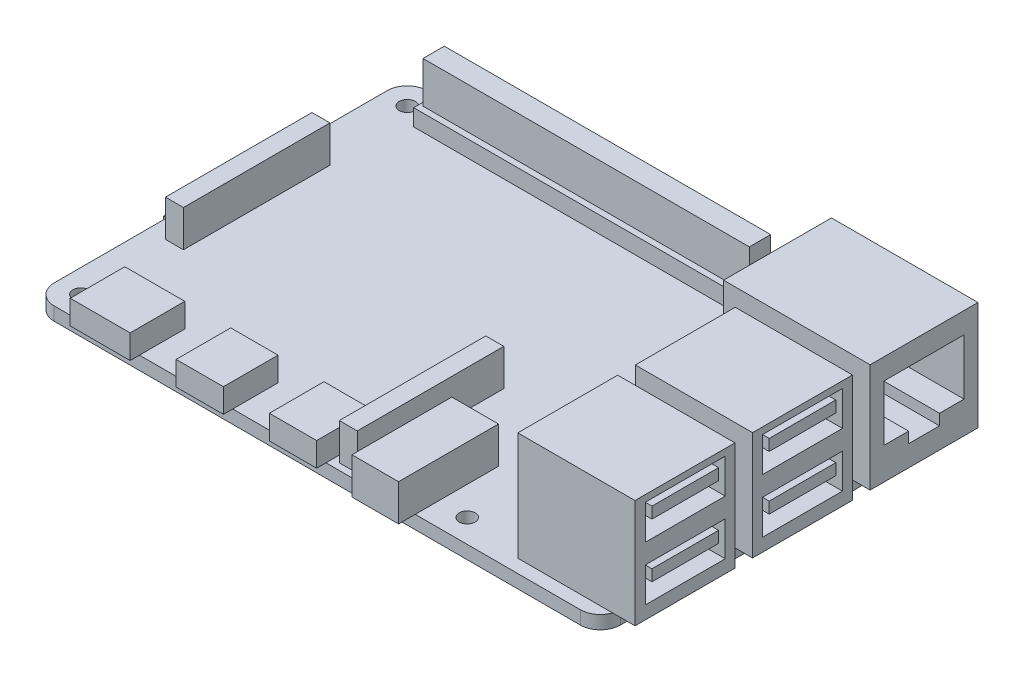
SolidWorks part; units mm, degrees
ref_plane "Plan de face" through (0, 0, 0) normal (0, 0, 1) x (1, 0, 0)
ref_plane "Plan de dessus" through (0, 0, 0) normal (0, 1, 0) x (1, 0, 0)
ref_plane "Plan de droite" through (0, 0, 0) normal (1, 0, 0) x (0, 0, -1)
sketch "Esquisse1" plane through (0, 0, 0) normal (0, 1, 0) x (1, 0, 0)
  line L1 (-42.5, 28) -> (42.5, 28)
  line L2 (-42.5, 28) -> (-42.5, -28)
  line L3 (-42.5, -28) -> (42.5, -28)
  line L4 (42.5, 28) -> (42.5, -28)
  line L5 (-42.5, 28) -> (42.5, -28) construction
  line L6 (-42.5, -28) -> (42.5, 28) construction
  point P0 (0, 0)
  dimension "D1" = 85
  dimension "D2" = 56
extrude "Boss.-Extru.1" add sketch "Esquisse1" along normal blind 2
hole_wizard "Dégagement M21" positions "Esquisse3D1" profile "Esquisse2" hole size "M2" standard "ISO" end condition up to next
sketch3d "Esquisse3D1"
  line L1 (-39, 2, -24.5) -> (-39, 2, 24.5)
  line L2 (-39, 2, -24.5) -> (19, 2, -24.5)
  line L3 (19, 2, -24.5) -> (19, 2, 24.5)
  line L4 (-39, 2, 24.5) -> (19, 2, 24.5)
  line L5 (-42.5, 2, -28) -> (-42.5, 2, 28) construction
  line L6 (42.5, 2, -28) -> (-42.5, 2, -28) construction
  point P0 (-39, 2, -24.5)
  point P2 (-39, 2, 24.5)
  point P4 (19, 2, -24.5)
  point P6 (19, 2, 24.5)
  dimension "D1" = 49
  dimension "D2" = 58
  dimension "D3" = 3.5
  dimension "D4" = 3.5
sketch "Esquisse2" plane through (-39, 2, -24.5) normal (1, 0, 0) x (0, 0, 1)
  line L0 (0, 0) -> (0, 2)
  line L1 (0, 2) -> (1.2, 2)
  line L2 (1.2, 2) -> (1.2, 0)
  line L5 (1.2, 0) -> (0, 0)
  line L11 (0, -6.35) -> (0, 107.95) construction
  dimension "Diamètre du perçage jusqu'au prochain" = 2.4
  dimension "Profondeur du perçage jusqu'au prochain" = 2
sketch "Esquisse4" plane through (0, 2, 0) normal (0, 1, 0) x (1, 0, 0)
  line L1 (-35.7959, 27.2655) -> (14.2041, 27.2655)
  line L2 (-35.7959, 27.2655) -> (-35.7959, 22.2655)
  line L3 (-35.7959, 22.2655) -> (14.2041, 22.2655)
  line L4 (14.2041, 27.2655) -> (14.2041, 22.2655)
  dimension "D1" = 5
  dimension "D2" = 50
extrude "Boss.-Extru.3" add sketch "Esquisse4" along normal blind 2.5
sketch "Esquisse6" plane through (0, 4.5, 0) normal (0, 1, 0) x (1, 0, 0)
  line L0 (-35.7959, 22.2655) -> (14.2041, 22.2655) construction
  line L1 (-35.2959, 26.3655) -> (13.7041, 26.3655)
  line L2 (-35.2959, 26.3655) -> (-35.2959, 23.1655)
  line L3 (-35.2959, 23.1655) -> (13.7041, 23.1655)
  line L4 (13.7041, 26.3655) -> (13.7041, 23.1655)
  line L5 (-35.7959, 27.2655) -> (-35.7959, 22.2655) construction
  point P4 (-10.7959, 23.1655)
  point P7 (-10.7959, 22.2655)
  point P8 (-35.2959, 24.7655)
  point P11 (-35.7959, 24.7655)
  dimension "D1" = 49
  dimension "D2" = 3.2
extrude "Boss.-Extru.5" add sketch "Esquisse6" along normal blind 6.2
sketch "Esquisse3" plane through (0, 2, 0) normal (0, 1, 0) x (1, 0, 0)
  line L0 (42.5, 28) -> (-42.5, 28) construction
  line L1 (23.7, 25.5) -> (45.7, 25.5)
  line L2 (23.7, 25.5) -> (23.7, 9.3)
  line L3 (28.1, -26) -> (45.7, -26)
  line L4 (45.7, 25.5) -> (45.7, 9.3)
  line L5 (-42.5, -28) -> (42.5, -28) construction
  line L6 (42.5, -28) -> (42.5, 28) construction
  line L7 (28.1, -11) -> (45.7, -11)
  line L8 (28.1, -8.35) -> (45.7, -8.35)
  line L9 (28.1, -11) -> (28.1, -26)
  line L10 (45.7, -11) -> (45.7, -26)
  line L11 (28.1, 6.65) -> (45.7, 6.65)
  line L12 (23.7, 9.3) -> (45.7, 9.3)
  line L13 (28.1, 6.65) -> (28.1, -8.35)
  line L14 (45.7, 6.65) -> (45.7, -8.35)
  line L15 (45.7, -11) -> (45.7, -8.35) construction
  line L16 (45.7, 6.65) -> (45.7, 9.3) construction
  dimension "D1" = 2.5
  dimension "D2" = 2
  dimension "D3" = 3.2
  dimension "D4" = 22
  dimension "D5" = 15
  dimension "D6" = 16.2
  dimension "D7" = 17.6
extrude "Boss.-Extru.2" add sketch "Esquisse3" along normal blind 16.3
sketch "Esquisse7" plane through (45.7, 0, 0) normal (1, 0, 0) x (0, 0, -1)
  line L6 (17.4, 5.15) -> (17.4, 15.15) construction
  line L7 (23.4, 15.15) -> (11.4, 15.15)
  line L8 (11.4, 15.15) -> (11.4, 6.7853)
  line L9 (11.4, 6.7853) -> (15.0804, 6.7853)
  line L10 (15.0804, 6.7853) -> (15.0804, 5.15)
  line L11 (15.0804, 5.15) -> (19.7196, 5.15)
  line L12 (19.7196, 6.7853) -> (19.7196, 5.15)
  line L13 (23.4, 6.7853) -> (19.7196, 6.7853)
  line L14 (23.4, 15.15) -> (23.4, 6.7853)
  line L15 (9.3, 18.3) -> (25.5, 18.3) construction
  line L16 (9.3, 18.3) -> (9.3, 2) construction
  line L17 (-8.35, 10.15) -> (-3.4275, 10.15) construction
  line L22 (-8.35, 18.3) -> (-8.35, 2) construction
  line L23 (-24.45, 17.3) -> (-24.45, 12.1)
  line L24 (-24.45, 17.3) -> (-12.45, 17.3)
  line L29 (-8.35, 18.3) -> (6.65, 18.3) construction
  line L39 (-6.85, 17.3) -> (5.15, 17.3)
  line L40 (-6.85, 17.3) -> (-6.85, 12.1)
  line L41 (-6.85, 12.1) -> (5.15, 12.1)
  line L42 (5.15, 17.3) -> (5.15, 12.1)
  line L43 (-5.85, 16.3) -> (4.15, 16.3)
  line L44 (-5.85, 16.3) -> (-5.85, 14.6)
  line L45 (-5.85, 14.6) -> (4.15, 14.6)
  line L46 (4.15, 16.3) -> (4.15, 14.6)
  line L47 (-12.45, 17.3) -> (-12.45, 12.1)
  line L48 (-24.45, 12.1) -> (-12.45, 12.1)
  line L49 (-23.45, 16.3) -> (-23.45, 14.6)
  line L50 (-23.45, 16.3) -> (-13.45, 16.3)
  line L51 (-13.45, 16.3) -> (-13.45, 14.6)
  line L52 (-23.45, 14.6) -> (-13.45, 14.6)
  line L53 (-24.45, 9.15) -> (-24.45, 3.95)
  line L54 (-24.45, 9.15) -> (-12.45, 9.15)
  line L55 (-12.45, 9.15) -> (-12.45, 3.95)
  line L56 (-24.45, 3.95) -> (-12.45, 3.95)
  line L57 (-23.45, 8.15) -> (-23.45, 6.45)
  line L58 (-23.45, 8.15) -> (-13.45, 8.15)
  line L59 (-13.45, 8.15) -> (-13.45, 6.45)
  line L60 (-23.45, 6.45) -> (-13.45, 6.45)
  line L61 (-6.85, 9.15) -> (-6.85, 3.95)
  line L62 (-6.85, 9.15) -> (5.15, 9.15)
  line L63 (5.15, 9.15) -> (5.15, 3.95)
  line L64 (-6.85, 3.95) -> (5.15, 3.95)
  line L65 (-5.85, 8.15) -> (-5.85, 6.45)
  line L66 (-5.85, 8.15) -> (4.15, 8.15)
  line L67 (4.15, 8.15) -> (4.15, 6.45)
  line L68 (-5.85, 6.45) -> (4.15, 6.45)
  point P12 (17.4, 18.3)
  point P13 (17.4, 10.15)
  point P16 (9.3, 10.15)
  point P25 (-0.85, 17.3)
  point P30 (-0.85, 14.6)
  point P31 (-0.85, 12.1)
  point P38 (-0.85, 18.3)
  dimension "D1" = 12
  dimension "D2" = 10
  dimension "D3" = 12
  dimension "D4" = 5.2
  dimension "D5" = 1.7
  dimension "D6" = 1
  dimension "D7" = 1
  dimension "D8" = 1
  dimension "D9" = 2
  dimension "D10" = 2
extrude "Enlèv. mat.-Extru.1" cut sketch "Esquisse7" against normal blind 12
sketch "Esquisse5" plane through (0, 2, 0) normal (0, 1, 0) x (1, 0, 0)
  line L0 (-42.5, 28) -> (-42.5, -28) construction
  line L5 (-35.7, -21.2) -> (-26.7, -21.2)
  line L6 (-35.7, -21.2) -> (-35.7, -29.4)
  line L7 (-35.7, -29.4) -> (-26.7, -29.4)
  line L8 (-26.7, -21.2) -> (-26.7, -29.4)
  line L9 (-19.8, -21.2) -> (-12.7, -21.2)
  line L10 (-19.8, -21.2) -> (-19.8, -29.4)
  line L11 (-19.8, -29.4) -> (-12.7, -29.4)
  line L12 (-12.7, -21.2) -> (-12.7, -29.4)
  line L13 (-5.8, -21.2) -> (1.3, -21.2)
  line L14 (-5.8, -21.2) -> (-5.8, -29.4)
  line L15 (-5.8, -29.4) -> (1.3, -29.4)
  line L16 (1.3, -21.2) -> (1.3, -29.4)
  line L17 (-42.5, -28) -> (42.5, -28) construction
  dimension "D1" = 6.8
  dimension "D2" = 6.9
  dimension "D3" = 9
  dimension "D4" = 7.1
  dimension "D5" = 6.9
  dimension "D6" = 1.4
  dimension "D7" = 8.2
extrude "Boss.-Extru.4" add sketch "Esquisse5" along normal blind 3.6
sketch "Esquisse8" plane through (0, 2, 0) normal (0, 1, 0) x (1, 0, 0)
  line L0 (1.3, -28) -> (42.5, -28) construction
  line L1 (7.7, -15.5) -> (14.7, -15.5)
  line L2 (7.7, -15.5) -> (7.7, -30.5)
  line L3 (7.7, -30.5) -> (14.7, -30.5)
  line L4 (14.7, -15.5) -> (14.7, -30.5)
  line L5 (42.5, -28) -> (42.5, -26) construction
  line L6 (-42.5, 28) -> (-42.5, -28) construction
  line L7 (5, -27) -> (2.3, -27)
  line L8 (5, -27) -> (5, -5)
  line L9 (5, -5) -> (2.3, -5)
  line L10 (2.3, -27) -> (2.3, -5)
  line L11 (-37.1, -11) -> (-39.8, -11)
  line L12 (-37.1, -11) -> (-37.1, 11)
  line L13 (-37.1, 11) -> (-39.8, 11)
  line L14 (-39.8, -11) -> (-39.8, 11)
  point P18 (-42.5, 0)
  point P19 (-39.8, 0)
  dimension "D1" = 15
  dimension "D2" = 2.5
  dimension "D3" = 27.8
  dimension "D4" = 7
  dimension "D5" = 2.7
  dimension "D6" = 22
  dimension "D7" = 2.7
  dimension "D8" = 2.7
  dimension "D9" = 1
extrude "Boss.-Extru.6" add sketch "Esquisse8" along normal blind 5.5
sketch "Esquisse9" plane through (0, 0, 0) normal (0, -1, 0) x (1, 0, 0)
  line L0 (-42.5, -28) -> (-42.5, 28) construction
  line L1 (-45, 6.1) -> (-29.5, 6.1)
  line L2 (-45, 6.1) -> (-45, -6.1)
  line L3 (-45, -6.1) -> (-29.5, -6.1)
  line L4 (-29.5, 6.1) -> (-29.5, -6.1)
  point P4 (-29.5, 0)
  dimension "D1" = 12.2
  dimension "D2" = 15.5
  dimension "D3" = 2.5
extrude "Boss.-Extru.7" add sketch "Esquisse9" along normal blind 1.5
fillet "Congé1" radius 3 4 edges at (42.5, 1, 28) (42.5, 1, -28) (-42.5, 1, 28) (-42.5, 1, -28)
ref_plane "Plan1" through (-31.2, 0, 0) normal (1, 0, 0) x (0, 0, -1)
ref_plane "Plan2" through (0, 3.8, 0) normal (0, 1, 0) x (1, 0, 0)
ref_plane "Plan3" through (0, 0, -17.4) normal (0, 0, 1) x (1, 0, 0)
ref_plane "Plan4" through (0, 10.9676, 0) normal (0, 1, 0) x (1, 0, 0)
equation "\"D5@Esquisse5\"=\"D2@Esquisse5\""
